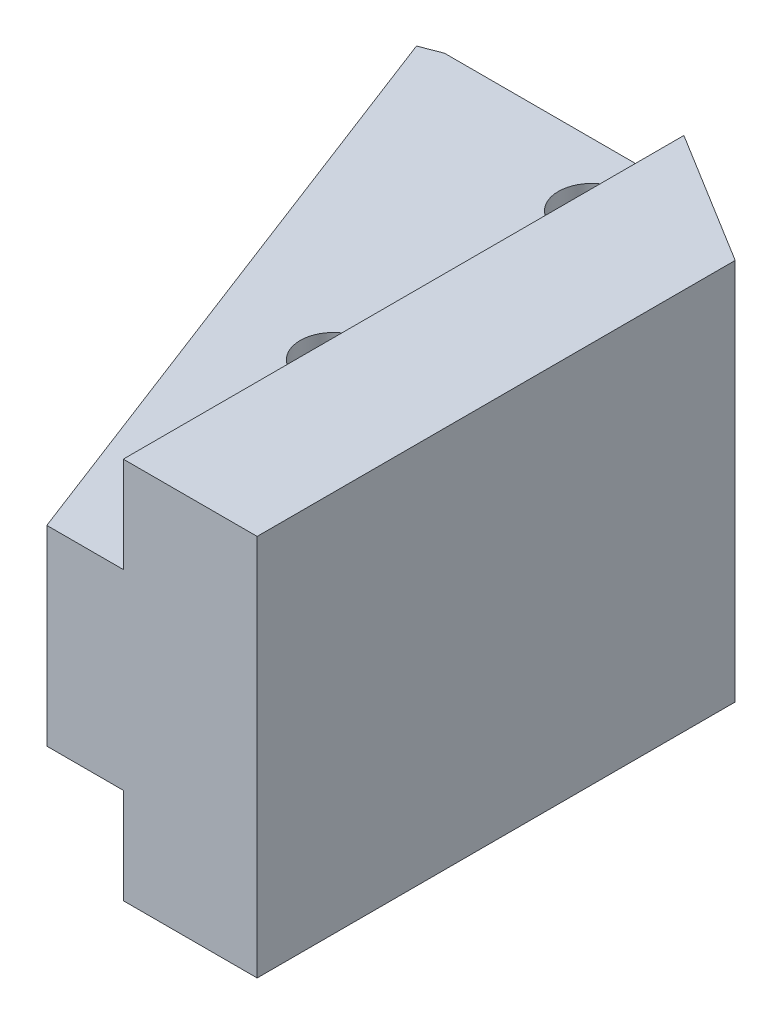
SolidWorks part; units mm, degrees
material "Gummi"
ref_plane "Ebene vorne" through (0, 0, 0) normal (0, 0, 1) x (1, 0, 0)
ref_plane "Ebene oben" through (0, 0, 0) normal (0, 1, 0) x (1, 0, 0)
ref_plane "Ebene rechts" through (0, 0, 0) normal (1, 0, 0) x (0, 0, -1)
sketch "Skizze1" plane through (0, 0, 0) normal (0, 0, 1) x (1, 0, 0)
  line L0 (0, 5) -> (0, -5)
  line L1 (0, -5) -> (4, -5)
  line L2 (4, -5) -> (4, -10)
  line L3 (4, -10) -> (11, -10)
  line L4 (11, -10) -> (11, 10)
  line L5 (11, 10) -> (4, 10)
  line L6 (4, 10) -> (4, 5)
  line L7 (4, 5) -> (0, 5)
  line L8 (0, 0) -> (27.3492, 0) construction
  dimension "D1" = 10
  dimension "D2" = 4
  dimension "D3" = 7
  dimension "D4" = 20
extrude "Aufsatz-Linear austragen1" add sketch "Skizze1" along normal blind 40
sketch "Skizze2" plane through (0, 5, 0) normal (0, 1, 0) x (1, 0, 0)
  line L0 (0, -40) -> (-12.0444, -8.6234)
  line L1 (-12.0444, -8.6234) -> (0, -4)
  line L2 (0, -40) -> (0, 0) construction
  line L3 (0, -4) -> (0, -40)
  line L4 (4, -40) -> (4, 0) construction
  point P3 (-12.3827, -7.8809)
  point P7 (-14.6579, -11.5527)
  point P8 (-11.9527, -8.5415)
  dimension "D1" = 36
  dimension "D2" = 21
extrude "Aufsatz-Linear austragen2" add sketch "Skizze2" against normal up to surface (10 mm away) up to face at (2, -5, 20)
sketch "Skizze4" plane through (0, 10, 0) normal (0, 1, 0) x (1, 0, 0)
  line L0 (-10.9852, -8.2168) -> (0, -8.2168)
  line L1 (0, -4) -> (-12.0444, -8.6234) construction
  line L2 (0, -8.2168) -> (11, -15)
  line L3 (11, -40) -> (11, 0) construction
  line L4 (-10.9852, -8.2168) -> (0, -4)
  line L5 (0, -4) -> (0, 0)
  line L6 (0, 0) -> (11, 0)
  line L7 (11, 0) -> (11, -15)
  dimension "D1" = 15
extrude "Schnitt-Linear austragen1" cut sketch "Skizze4" against normal up to surface (20 mm away) up to face at (7.5, -10, 20)
sketch "Skizze5" plane through (0, 10, 0) normal (0, 1, 0) x (1, 0, 0)
  line L0 (11, -40) -> (4, -40) construction
  line L1 (4, -40) -> (4, -10.6834) construction
  line L2 (4, -40) -> (0, -40) construction
  circle A0 centre (0, -25) radius 1.75
  circle A1 centre (0, -11.5) radius 1.75
  point P9 (0, -11.4668)
  point P11 (0, -10.8563)
  point P12 (0, -11.3881)
  dimension "D1" = 3.5
  dimension "D3" = 3.5
  dimension "D2" = 15
  dimension "D4" = 4
  dimension "D5" = 4
  dimension "D6" = 28.5
extrude "Schnitt-Linear austragen2" cut sketch "Skizze5" against normal through all both and the other way through all
sketch "Skizze6" plane through (11, 0, 0) normal (1, 0, 0) x (0, 0, -1)
  line L0 (-40, 10) -> (-15, 10) construction
  line L1 (-39, 10) -> (-37, 10)
  line L2 (-39, 10) -> (-39, -10)
  line L3 (-39, -10) -> (-37, -10)
  line L4 (-37, 10) -> (-37, -10)
  line L5 (-40, -10) -> (-15, -10) construction
  line L6 (-40, -10) -> (-40, 10) construction
  line L7 (-36, 10) -> (-34, 10)
  line L8 (-36, 10) -> (-36, -10)
  line L9 (-36, -10) -> (-34, -10)
  line L10 (-34, 10) -> (-34, -10)
  line L11 (-33, 10) -> (-31, 10)
  line L12 (-33, 10) -> (-33, -10)
  line L13 (-33, -10) -> (-31, -10)
  line L14 (-31, 10) -> (-31, -10)
  line L15 (-30, 10) -> (-28, 10)
  line L16 (-30, 10) -> (-30, -10)
  line L17 (-30, -10) -> (-28, -10)
  line L18 (-28, 10) -> (-28, -10)
  line L19 (-27, 10) -> (-25, 10)
  line L20 (-27, 10) -> (-27, -10)
  line L21 (-27, -10) -> (-25, -10)
  line L22 (-25, 10) -> (-25, -10)
  line L23 (-24, 10) -> (-22, 10)
  line L24 (-24, 10) -> (-24, -10)
  line L25 (-24, -10) -> (-22, -10)
  line L26 (-22, 10) -> (-22, -10)
  line L27 (-21, 10) -> (-19, 10)
  line L28 (-21, 10) -> (-21, -10)
  line L29 (-21, -10) -> (-19, -10)
  line L30 (-19, 10) -> (-19, -10)
  line L31 (-18, 10) -> (-16, 10)
  line L32 (-18, 10) -> (-18, -10)
  line L33 (-18, -10) -> (-16, -10)
  line L34 (-16, 10) -> (-16, -10)
  dimension "D1" = 1
  dimension "D2" = 2
  dimension "D3" = 8
extrude "Schnitt-Linear austragen3" [suppressed] cut sketch "Skizze6" against normal blind 1
sketch "Skizze7" plane through (11, 0, 0) normal (1, 0, 0) x (0, 0, -1)
  line L0 (-40, -10) -> (-40, 10) construction
  line L1 (-40, 9) -> (-10.6834, 9)
  line L2 (-40, 9) -> (-40, 7)
  line L3 (-40, 7) -> (-10.6834, 7)
  line L4 (-10.6834, 9) -> (-10.6834, 7)
  line L6 (-10.6834, 10) -> (-15, 10) construction
  line L7 (-10.6834, 10) -> (-10.6834, 5) construction
  line L8 (-40, 6) -> (-10.6834, 6)
  line L9 (-40, 6) -> (-40, 4)
  line L10 (-40, 4) -> (-10.6834, 4)
  line L11 (-10.6834, 6) -> (-10.6834, 4)
  line L12 (-40, 3) -> (-10.6834, 3)
  line L13 (-40, 3) -> (-40, 1)
  line L14 (-40, 1) -> (-10.6834, 1)
  line L15 (-10.6834, 3) -> (-10.6834, 1)
  line L16 (-40, 0) -> (-10.6834, 0)
  line L17 (-40, 0) -> (-40, -2)
  line L18 (-40, -2) -> (-10.6834, -2)
  line L19 (-10.6834, 0) -> (-10.6834, -2)
  line L20 (-40, -3) -> (-10.6834, -3)
  line L21 (-40, -3) -> (-40, -5)
  line L22 (-40, -5) -> (-10.6834, -5)
  line L23 (-10.6834, -3) -> (-10.6834, -5)
  line L24 (-40, -6) -> (-10.6834, -6)
  line L25 (-40, -6) -> (-40, -8)
  line L26 (-40, -8) -> (-10.6834, -8)
  line L27 (-10.6834, -6) -> (-10.6834, -8)
  point P10 (-12.8417, 10)
  dimension "D1" = 1
  dimension "D2" = 2
  dimension "D3" = 6
extrude "Schnitt-Linear austragen4" [suppressed] cut sketch "Skizze7" against normal blind 1
